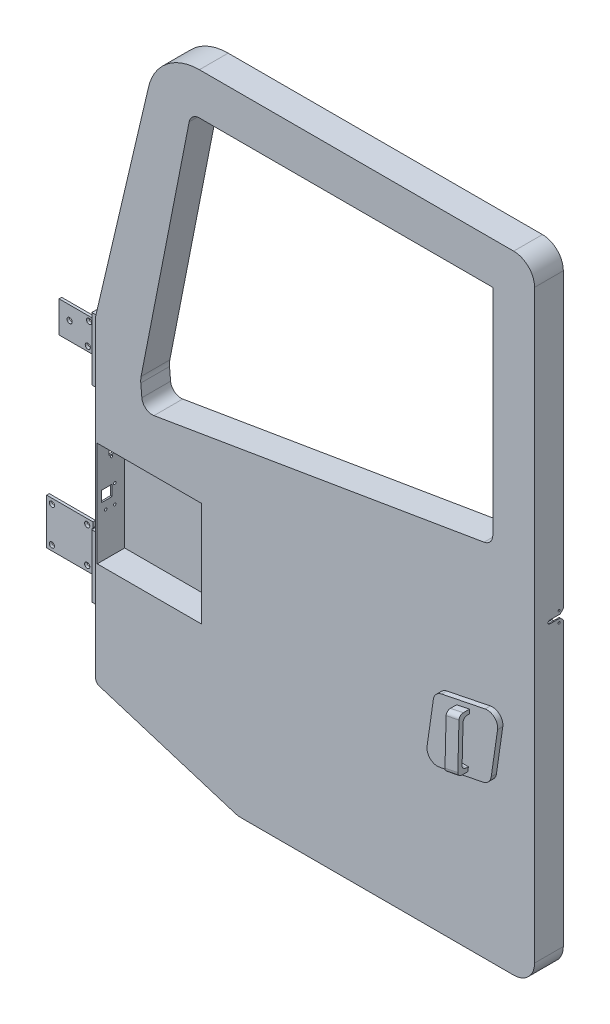
SolidWorks part; units mm, degrees
ref_plane "Front Plane" through (0, 0, 0) normal (0, 0, 1) x (1, 0, 0)
ref_plane "Top Plane" through (0, 0, 0) normal (0, 1, 0) x (1, 0, 0)
ref_plane "Right Plane" through (0, 0, 0) normal (1, 0, 0) x (0, 0, -1)
sketch "Sketch2" plane through (0, 0, 0) normal (0, 0, 1) x (1, 0, 0)
  line L1 (-179.7693, -762.022) -> (482.6, -762.022)
  line L3 (-281.2299, 761.978) -> (482.6, 761.978)
  line L4 (533.4, -711.222) -> (533.4, 711.178)
  line L5 (-459.8603, -656.939) -> (-452.0517, -645.784) construction
  line L6 (-417.9715, 597.0829) -> (44.2876, -63.266) construction
  line L8 (-524.4721, -657.2008) -> (-194.8579, -759.7295)
  line L9 (-306.1723, 639.7777) -> (-423.0219, 45.4039)
  line L10 (-423.7768, 31.1096) -> (-421.1458, 1.4921)
  line L14 (-281.2299, 660.378) -> (431.8, 660.378)
  line L16 (431.7996, 138.4174) -> (431.8, 660.378)
  line L17 (431.8, -660.422) -> (431.8, 660.378) construction
  line L18 (-172.0509, -660.422) -> (431.8, -660.422) construction
  line L19 (-533.4, 116.926) -> (-405.8883, 659.253)
  line L20 (-367.7549, -599.547) -> (-172.0509, -660.422) construction
  line L21 (-55.7209, -79.6007) -> (521.0599, 744.3665) construction
  line L22 (-306.1723, 639.7777) -> (-424.4164, 38.3105) construction
  line L23 (-424.4164, 38.3105) -> (-367.7549, -599.547) construction
  line L24 (-414.3579, -691.4526) -> (-194.8579, -759.7295) construction
  line L25 (-179.7693, -762.022) -> (482.6, -762.022)
  line L27 (-281.2299, 761.978) -> (482.6, 761.978)
  line L28 (533.4, -711.222) -> (533.4, 711.178)
  line L29 (-459.8603, -656.939) -> (-452.0517, -645.784) construction
  line L30 (-417.9715, 597.0829) -> (44.2876, -63.266) construction
  line L31 (-533.4, 116.926) -> (-466.2749, -638.723) construction
  line L32 (-391.6402, -21.3099) -> (410.6048, 113.3679)
  line L33 (-55.7209, -79.6007) -> (521.0599, 744.3665) construction
  line L34 (-281.2299, 761.978) -> (482.6, 761.978)
  line L35 (-533.4, 116.926) -> (-533.4, -645.074)
  line L36 (-179.7693, -762.022) -> (482.6, -762.022)
  line L37 (533.4, 711.178) -> (533.4, -711.222)
  line L38 (-417.9715, 597.0829) -> (44.2876, -63.266) construction
  line L39 (-471.5639, -673.6583) -> (-452.0517, -645.784) construction
  line L40 (-405.8883, 659.253) -> (-528.8132, 33.9764) construction
  line L41 (-55.7209, -79.6007) -> (521.0599, 744.3665) construction
  arc A0 (-405.8883, 659.253) -> (-281.2299, 761.978) centre (-281.2299, 634.978) cw
  arc A3 (533.4, 711.178) -> (482.6, 761.978) centre (482.6, 711.178) ccw
  arc A4 (482.6, -762.022) -> (533.4, -711.222) centre (482.6, -711.222) ccw
  arc A5 (-194.8579, -759.7295) -> (-179.7693, -762.022) centre (-179.7693, -711.222) ccw
  arc A7 (-367.7549, -599.547) -> (-367.7549, -599.547) centre (-367.7549, -599.547) ccw
  arc A8 (-172.0509, -660.422) -> (-172.0509, -660.422) centre (-172.0509, -660.422) ccw
  arc A9 (431.8, -660.422) -> (431.8, -660.422) centre (431.8, -660.422) ccw
  arc A10 (431.8, 660.378) -> (431.8, 660.378) centre (431.8, 660.378) ccw
  arc A11 (-306.1723, 639.7777) -> (-281.2299, 660.378) centre (-281.2299, 634.978) cw
  arc A12 (-423.0219, 45.4039) -> (-423.7768, 31.1096) centre (-373.176, 35.6045) ccw
  arc A13 (-424.4164, 38.3105) -> (-424.4164, 38.3105) centre (-424.4164, 38.3105) ccw construction
  arc A16 (-466.2749, -638.723) -> (-414.3579, -691.4526) centre (-391.0208, -616.5518) ccw construction
  arc A17 (-533.4, -645.074) -> (-524.4721, -657.2008) centre (-520.7, -645.074) ccw
  arc A18 (-528.8132, 33.9764) -> (-533.4, 116.926) centre (-501.9071, 77.0658) ccw construction
  arc A19 (431.7996, 138.4174) -> (410.6048, 113.3679) centre (406.3996, 138.4174) cw
  arc A20 (-391.6402, -21.3099) -> (-421.1458, 1.4921) centre (-395.8454, 3.7395) cw
  point P0 (0, 0)
  point P16 (-533.4, -0.0244)
  point P56 (0, 0)
  point P61 (0, 0)
  dimension "D3" = 127
  dimension "D6" = 50.8
  dimension "D8" = 50.8
  dimension "D2" = 12.7
  dimension "D9" = 25.4
  dimension "D1" = 1066.8
  dimension "D4" = 1524
  dimension "D5" = 762
  dimension "D7" = 101.6
extrude "Boss-Extrude1" add sketch "Sketch2" along normal mid plane 69.85 contours L8 A5 L1 A4 L4 A3 L3 A0 L10 A12 L9 A11 L14 L16 A20 region at (22.1716, -171.0663, 0)
ref_plane "bottom" through (0, -762.022, 0) normal (0, -1, 0) x (-1, 0, 0)
ref_plane "top door check" through (0, -158.772, 0) normal (0, -1, 0) x (-1, 0, 0)
ref_plane "door check mid" through (0, -176.2345, 0) normal (0, -1, 0) x (-1, 0, 0)
ref_plane "bottom door check" through (0, -193.697, 0) normal (0, -1, 0) x (-1, 0, 0)
ref_plane "top hinge top hole" through (0, 66.653, 0) normal (0, -1, 0) x (-1, 0, 0)
ref_plane "top hinge middle hole" through (0, 44.428, 0) normal (0, -1, 0) x (-1, 0, 0)
ref_plane "top hinge bottom hole" through (0, 12.678, 0) normal (0, -1, 0) x (-1, 0, 0)
ref_plane "bottome hinge top hole" through (0, -363.5595, 0) normal (0, -1, 0) x (-1, 0, 0)
ref_plane "bottom hinge bottom hole" through (0, -449.2845, 0) normal (0, -1, 0) x (-1, 0, 0)
ref_plane "Plane1" through (0, 0, 31.75) normal (0, 0, 1) x (1, 0, 0)
sketch "Sketch3" plane through (0, 0, 34.925) normal (0, 0, 1) x (1, 0, 0)
  line L0 (320.1959, -245.101) -> (425.9265, -223.6716)
  line L3 (314.9201, -401.6691) -> (420.6507, -380.2397)
  line L4 (456.113, -252.1835) -> (440.7462, -358.9639)
  line L5 (300.1004, -266.3768) -> (284.7336, -373.1572)
  line L6 (310.4001, -194.8067) -> (287.3499, -354.9772) construction
  line L7 (-487.6326, -408.8312) -> (533.4008, -201.8888) construction
  line L8 (-457.3598, -558.1943) -> (563.6737, -351.2518) construction
  line L9 (461.2461, -216.515) -> (438.1959, -376.6855) construction
  line L10 (373.0612, -234.3863) -> (367.7854, -390.9544) construction
  line L11 (360.2667, -236.9795) -> (354.9908, -393.5476)
  line L12 (385.8558, -231.7931) -> (380.58, -388.3612)
  line L13 (360.3684, -233.9586) -> (355.0926, -390.5267) construction
  line L14 (385.754, -234.814) -> (380.4782, -391.3821) construction
  arc A0 (300.1004, -266.3768) -> (320.1959, -245.101) centre (325.2414, -269.9949) cw
  arc A1 (284.7336, -373.1572) -> (314.9201, -401.6691) centre (309.8746, -376.7752) ccw
  arc A2 (440.7462, -358.9639) -> (420.6507, -380.2397) centre (415.6052, -355.3458) cw
  arc A3 (456.113, -252.1835) -> (425.9265, -223.6716) centre (430.972, -248.5655) ccw
  dimension "D3" = 25.4
  dimension "D1" = 152.4
  dimension "D2" = 152.4
  dimension "D4" = 12.7
  dimension "D5" = 12.7
extrude "Boss-Extrude2" add sketch "Sketch3" along normal blind 12.7 contours L5 A1 L3 L11 L0 A0 | L4 A3 L0 L12 L3 A2 | L12 L0 L11 L3 region at (325.2101, -323.7797, 34.925) region at (370.4233, -312.6704, 34.925) region at (415.6365, -301.561, 34.925)
sketch "Sketch5" plane through (0, 0, 34.925) normal (0, 0, 1) x (1, 0, 0)
  line L6 (-179.7693, -762.022) -> (482.6, -762.022)
  line L12 (-179.7693, -762.022) -> (482.6, -762.022)
  line L28 (387.9598, -243.0291) -> (384.7172, -375.8602)
  line L29 (353.4927, -382.1888) -> (356.7353, -249.3577)
  line L30 (387.9598, -243.0291) -> (356.7353, -249.3577)
  line L31 (384.7172, -375.8602) -> (353.4927, -382.1888)
  line L32 (320.1959, -245.101) -> (425.9265, -223.6716) construction
  line L33 (314.9201, -401.6691) -> (420.6507, -380.2397) construction
  line L34 (320.1959, -245.101) -> (425.9265, -223.6716) construction
  line L35 (314.9201, -401.6691) -> (420.6507, -380.2397) construction
  dimension "D2" = 11.43
  dimension "D3" = 11.43
  dimension "D1" = 0
extrude "Boss-Extrude4" add sketch "Sketch5" along normal blind 38.1 contours L31 L28 L30 L29 region at (370.7262, -312.609, 34.925)
sketch "Sketch6" plane through (393.6581, -9.61, 0) normal (0.9997, -0.0244, 0) x (0, 0, -1)
  line L9 (-47.625, -356.1994) -> (-62.865, -356.1994)
  line L10 (-62.865, -356.1994) -> (-62.865, -243.6487)
  line L11 (-62.865, -243.6487) -> (-47.625, -243.6487)
  line L12 (-47.625, -356.1994) -> (-62.865, -356.1994)
  line L13 (-62.865, -356.1994) -> (-62.865, -243.6487)
  line L14 (-62.865, -243.6487) -> (-47.625, -243.6487)
  line M5 (-47.625, -366.3594) -> (-47.625, -233.4887)
  dimension "D1" = 10.16
extrude "Cut-Extrude6" cut sketch "Sketch6" against normal through all and the other way through all contours L14 L13 L12 M5 region at (386.3385, -309.4447, 55.245)
fillet "Fillet5" radius 10.16 4 edges at (369.1049, -379.0245, 73.025) (369.4394, -365.3242, 62.865) (372.1861, -252.8071, 62.865) (372.3476, -246.1934, 73.025)
sketch "Sketch7" plane through (-533.4, 59.3738, 0) normal (1, 0, 0) x (0, 0, 1)
  line L0 (0, 821.3958) -> (0, -702.6042) construction
  line L1 (34.925, 821.3958) -> (-34.925, 821.3958) construction
  line L2 (34.925, -702.6042) -> (-34.925, -702.6042) construction
  line L4 (-31.75, -57.5522) -> (31.75, -57.5522)
  line L5 (-31.75, -57.5522) -> (-31.75, 94.8478)
  line L6 (-31.75, 94.8478) -> (31.75, 94.8478)
  line L11 (31.75, -57.5522) -> (31.75, 94.8478)
  line L12 (-31.75, -57.5522) -> (31.75, 94.8478) construction
  line L13 (-31.75, 94.8478) -> (31.75, -57.5522) construction
  line L19 (34.925, -57.5522) -> (-34.925, -57.5522) construction
  line L21 (-31.75, 552.0478) -> (31.75, 552.0478)
  line L28 (-31.75, 552.0478) -> (-31.75, 399.6478)
  line L29 (-31.75, 399.6478) -> (31.75, 399.6478)
  line L30 (31.75, 552.0478) -> (31.75, 399.6478)
  line L31 (-31.75, 552.0478) -> (31.75, 399.6478) construction
  line L32 (-31.75, 399.6478) -> (31.75, 552.0478) construction
  point P6 (0, 18.6478)
  point P13 (0, 475.8478)
  dimension "D1" = 63.5
  dimension "D2" = 152.4
  dimension "D4" = 304.8
extrude "Boss-Extrude5" add sketch "Sketch7" against normal blind 12.7
sketch "Sketch16" plane through (0, 0, 34.925) normal (0, 0, 1) x (1, 0, 0)
  line L1 (-529.59, -148.3099) -> (-529.59, -402.3099)
  line L3 (-275.59, -402.3099) -> (-275.59, -148.3099)
  line L5 (-533.4, 116.926) -> (-533.4, -645.074) construction
  line L6 (-529.59, -148.3099) -> (-275.59, -148.3099)
  line L7 (-529.59, -402.3099) -> (-275.59, -402.3099)
  dimension "D1" = 254
  dimension "D2" = 127
  dimension "D3" = 254
  dimension "D4" = 3.81
extrude "Cut-Extrude8" cut sketch "Sketch16" against normal blind 66.675
sketch "Sketch20" plane through (-533.4, 0, 0) normal (-1, 0, 0) x (0, 0, 1)
  line L0 (-38.4175, -176.2345) -> (38.4175, -176.2345) construction
  line L1 (-6.35, -188.9345) -> (6.35, -188.9345)
  line L2 (-6.35, -188.9345) -> (-6.35, -163.5345)
  line L3 (-6.35, -163.5345) -> (6.35, -163.5345)
  line L4 (6.35, -188.9345) -> (6.35, -163.5345)
  line L5 (-6.35, -188.9345) -> (6.35, -163.5345) construction
  line L6 (-6.35, -163.5345) -> (6.35, -188.9345) construction
  line L7 (-38.4175, -158.772) -> (38.4175, -158.772) construction
  line L8 (6.35, -176.2345) -> (-6.35, -176.2345) construction
  circle A0 centre (0, -158.772) radius 2.54
  circle A1 centre (0, -193.697) radius 2.54
  point P0 (0, -176.2345)
  dimension "D3" = 5.08
  dimension "D1" = 12.7
  dimension "D2" = 25.4
extrude "Cut-Extrude12" cut sketch "Sketch20" against normal up to surface (3.81 mm away) contours A0 | L4 L3 L2 L1 | A1 up to face at (-529.59, -275.3099, 1.5875)
sketch "Sketch21" plane through (0, 0, 0) normal (0, 0, 1) x (1, 0, 0)
  line L0 (-38.4175, 66.653) -> (38.4175, 66.653) construction
  line L1 (-202.423, 66.653) -> (-1027.3811, 66.653) construction
  line L2 (-212.5576, 44.428) -> (-1027.3811, 44.428) construction
  line L3 (-38.4175, 44.428) -> (38.4175, 44.428) construction
  line L4 (-212.5576, 12.678) -> (-1027.3811, 12.678) construction
  line L5 (-38.4175, 12.678) -> (38.4175, 12.678) construction
  line L6 (-546.1, 116.926) -> (-546.1, -35.474) construction
  line L7 (-558.8, 66.653) -> (-546.1, 66.653)
  line L8 (-558.8, 66.653) -> (-558.8, 12.678)
  line L9 (-558.8, 12.678) -> (-546.1, 12.678)
  line L10 (-546.1, 66.653) -> (-546.1, 12.678)
  line L11 (-654.05, 77.448) -> (-654.05, 1.248)
  line L12 (-654.05, 77.448) -> (-558.8, 77.448)
  line L15 (-558.8, 77.448) -> (-558.8, 12.678)
  line L16 (-654.05, 77.448) -> (-558.8, 12.678) construction
  line L17 (-654.05, 10.0872) -> (-558.8, 77.448) construction
  line L18 (-654.05, 1.248) -> (-558.8, 1.248)
  line L19 (-558.8, 12.678) -> (-558.8, 1.248)
  circle A0 centre (-584.2, 12.678) radius 6.35
  circle A1 centre (-628.65, 44.428) radius 6.35
  circle A2 centre (-581.025, 66.653) radius 6.35
  point P18 (-605.4912, 44.428)
  dimension "D2" = 12.7
  dimension "D3" = 25.4
  dimension "D4" = 69.85
  dimension "D5" = 22.225
  dimension "D6" = 95.25
  dimension "D9" = 64.77
  dimension "D1" = 12.7
  dimension "D7" = 76.2
  dimension "D8" = 33.02
extrude "Boss-Extrude8" add sketch "Sketch21" along normal mid plane 6.35 contours L19 L8 L15 L12 L11 L18 A2 A1 A0 | L10 L7 L8 L9 region at (-552.45, 39.6655, 0) region at (-606.8928, 39.2427, 0)
sketch "Sketch26" plane through (0, 0, 0) normal (0, 0, 1) x (1, 0, 0)
  line L0 (-193.6896, -363.5595) -> (-881.8717, -363.5595) construction
  line L1 (-38.4175, -363.5595) -> (38.4175, -363.5595) construction
  line L2 (-133.4597, -449.2845) -> (-881.8717, -449.2845) construction
  line L3 (-38.4175, -449.2845) -> (38.4175, -449.2845) construction
  line L4 (-625.8948, -363.5595) -> (-625.8948, -449.2845) construction
  line L5 (-625.8948, -406.422) -> (-892.4677, -406.422) construction
  line L6 (-546.1, -340.274) -> (-546.1, -492.674) construction
  line L7 (-571.5, -449.2845) -> (-546.1, -449.2845)
  line L8 (-571.5, -449.2845) -> (-571.5, -363.5595)
  line L9 (-571.5, -363.5595) -> (-546.1, -363.5595)
  line L10 (-546.1, -449.2845) -> (-546.1, -363.5595)
  line L11 (-571.5, -449.2845) -> (-546.1, -363.5595) construction
  line L12 (-571.5, -363.5595) -> (-546.1, -449.2845) construction
  point P12 (-558.8, -406.422)
  dimension "D1" = 25.4
extrude "Boss-Extrude12" add sketch "Sketch26" along normal mid plane 12.7
sketch "Sketch27" plane through (0, 0, 0) normal (0, 0, 1) x (1, 0, 0)
  line L0 (-211.2814, -363.5595) -> (-919.4505, -363.5595) construction
  line L1 (-38.4175, -363.5595) -> (38.4175, -363.5595) construction
  line L2 (-201.3631, -449.2845) -> (-928.7076, -449.2845) construction
  line L3 (-38.4175, -449.2845) -> (38.4175, -449.2845) construction
  line L4 (-571.5, -363.5595) -> (-571.5, -449.2845) construction
  line L5 (-631.7994, -363.5595) -> (-631.7994, -449.2845) construction
  line L6 (-631.7994, -406.422) -> (-919.4505, -406.422) construction
  line L8 (-684.2125, -461.9845) -> (-571.5, -461.9845)
  line L9 (-684.2125, -461.9845) -> (-684.2125, -350.8595)
  line L10 (-684.2125, -350.8595) -> (-571.5, -350.8595)
  line L11 (-571.5, -461.9845) -> (-571.5, -350.8595)
  line L12 (-684.2125, -461.9845) -> (-571.5, -350.8595) construction
  line L13 (-684.2125, -350.8595) -> (-571.5, -461.9845) construction
  circle A0 centre (-585.7875, -363.5595) radius 6.35
  circle A2 centre (-671.5125, -449.2845) radius 6.35
  circle A4 centre (-585.7875, -449.2845) radius 6.35
  circle A5 centre (-671.5125, -363.5595) radius 6.35
  point P22 (-627.8563, -406.422)
  dimension "D1" = 12.7
  dimension "D2" = 100.0125
  dimension "D3" = 14.2875
  dimension "D4" = 12.7
extrude "Boss-Extrude13" add sketch "Sketch27" along normal mid plane 6.35
sketch "Sketch28" plane through (-533.4, 0, 0) normal (-1, 0, 0) x (0, 0, 1)
  line L4 (24.765, -252.697) -> (24.765, -278.697)
  line L5 (34.925, -245.101) -> (34.925, -223.6716) construction
  line L6 (-38.4175, -193.697) -> (38.4175, -193.697) construction
  line L8 (24.765, -278.697) -> (-1.235, -278.697)
  line L9 (24.765, -278.697) -> (24.765, -252.697)
  line L10 (24.765, -252.697) -> (-1.235, -252.697)
  line L11 (-1.235, -278.697) -> (-1.235, -252.697)
  circle A7 centre (-7.705, -253.397) radius 3
  circle A8 centre (-7.705, -298.397) radius 3
  circle A9 centre (14.375, -298.397) radius 3
  point P16 (24.765, -265.697)
  dimension "D4" = 45
  dimension "D5" = 26
  dimension "D2" = 26
  dimension "D3" = 22.08
  dimension "D8" = 10.16
  dimension "D7" = 6
  dimension "D10" = 72
extrude "Cut-Extrude13" cut sketch "Sketch28" against normal up to surface (3.81 mm away) contours L4 | A8 | A9 | A7 region at (-533.4, -265.697, 11.765) region at (-533.4, -298.397, -7.705) region at (-533.4, -298.397, 14.375) up to face at (-529.59, -176.2345, 0)
sketch "Sketch29" plane through (533.4, 0, 0) normal (1, 0, 0) x (0, 0, -1)
  line L0 (34.925, -762.022) -> (34.925, -15.897)
  line L1 (34.925, -711.222) -> (34.925, 711.178) construction
  line L2 (27.305, -15.897) -> (1.9385, -15.897)
  line L3 (34.925, -0.022) -> (34.925, -23.517)
  line L4 (1.9385, -7.642) -> (27.305, -7.642)
  line L5 (27.305, -7.642) -> (34.925, -0.022)
  line L6 (27.305, -15.897) -> (34.925, -23.517)
  arc A0 (1.9385, -7.642) -> (1.9385, -15.897) centre (1.9385, -11.7695) ccw
  line M2 (34.925, -711.222) -> (34.925, 711.178)
extrude "Cut-Extrude14" cut sketch "Sketch29" against normal blind 2.54 contours L4 A0 L2 L6 L0 L5 M2 region at (533.4, -11.7695, -19.3332)
sketch "Sketch30" plane through (0, 0, -34.925) normal (0, 0, -1) x (-1, 0, 0)
  line L0 (-530.86, -11.7695) -> (-530.86, 64.4305)
  line L1 (-530.86, -23.517) -> (-530.86, -0.022) construction
  line L2 (-530.86, 64.4305) -> (-505.46, 64.4305)
  line L3 (-505.46, 64.4305) -> (-505.46, -37.1695)
  line L4 (-505.46, -37.1695) -> (-530.86, -37.1695)
  line L5 (-530.86, -37.1695) -> (-530.86, -11.7695)
extrude "Cut-Extrude15" cut sketch "Sketch30" against normal blind 65.1
sketch "Sketch31" plane through (533.4, 0, 0) normal (1, 0, 0) x (0, 0, -1)
  line L0 (34.925, 13.6305) -> (34.925, 0.9305)
  line L1 (34.925, -37.1695) -> (34.925, 64.4305) construction
  line L2 (34.925, -0.022) -> (34.925, 711.178) construction
  line L3 (34.925, 0.9305) -> (24.765, 0.9305)
  line L4 (24.765, 0.9305) -> (24.765, -24.4695)
  circle A0 centre (24.765, 0.9305) radius 2.54
  circle A1 centre (24.765, -24.4695) radius 2.54
extrude "Cut-Extrude16" cut sketch "Sketch31" against normal blind 10.668 contours L4 A0 L3 | L3 A0 L4 | A1 region at (533.4, -0.1475, -25.843) region at (533.4, 1.2898, -24.4057) region at (533.4, -22.7243, -26.5103)
equation "\"doorwidth\"= 42in"
equation "\"D1@Sketch2\"=\"doorwidth\""
equation "\"doorheight\"= 60in"
equation "\"D4@Sketch2\"=\"doorheight\""
equation "\"doorthickness\"= 2.75in"
equation "\"D1@Boss-Extrude1\"=\"doorthickness\""
equation "\"hingewidth\"= 2.5in"
equation "\"hingeheight\"= 6in"
equation "\"distanceofhinges\"= 12in"
equation "\"D1@Sketch7\"=\"hingewidth\""
equation "\"D2@Sketch7\"=\"hingeheight\""
equation "\"D4@Sketch7\"=\"distanceofhinges\""
